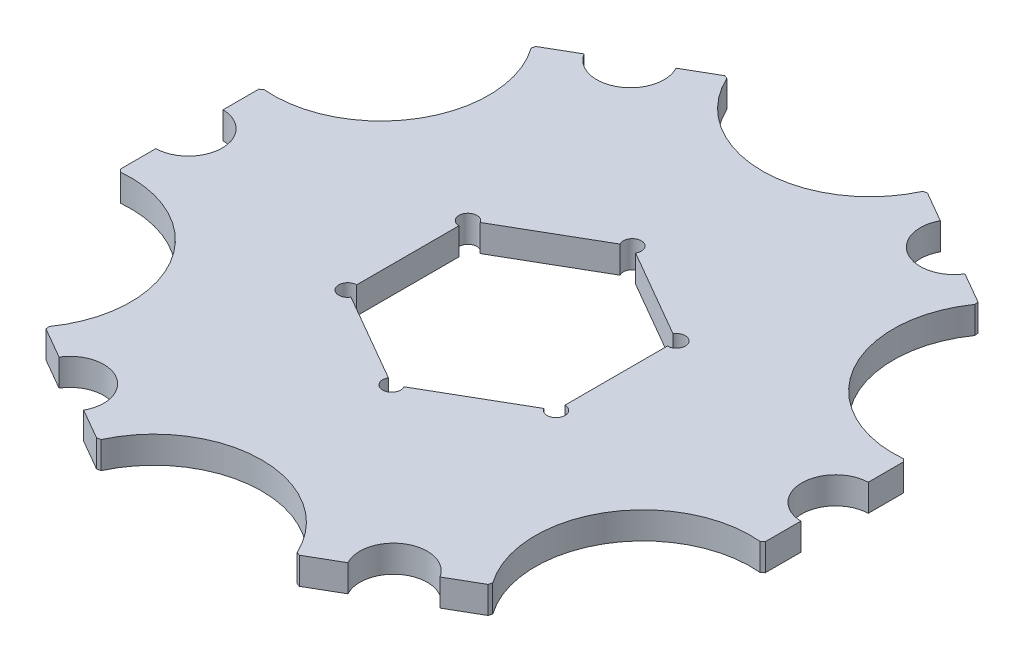
SolidWorks part; units mm, degrees
material "7075-T6 (SN)"
ref_plane "Front Plane" through (0, 0, 0) normal (0, 0, 1) x (1, 0, 0)
ref_plane "Top Plane" through (0, 0, 0) normal (0, 1, 0) x (1, 0, 0)
ref_plane "Right Plane" through (0, 0, 0) normal (1, 0, 0) x (0, 0, -1)
sketch "Sketch1" plane through (0, 0, 0) normal (0, 1, 0) x (1, 0, 0)
  line L0 (0, 0) -> (-62.5623, 0) construction
  line L1 (18.4023, 10.6246) -> (0, 21.2491)
  line L2 (0, 21.2491) -> (-18.4023, 10.6246)
  line L3 (-18.4023, 10.6246) -> (-18.4023, -10.6246)
  line L4 (-18.4023, -10.6246) -> (0, -21.2491)
  line L5 (0, -21.2491) -> (18.4023, -10.6246)
  line L6 (18.4023, -10.6246) -> (18.4023, 10.6246)
  line L7 (-56.9722, 12.7) -> (-56.9722, 5.9505)
  line L8 (-57.15, 0) -> (-57.15, -29.149) construction
  line L9 (-56.9722, -5.9505) -> (-56.9722, -12.7)
  line L10 (-33.6394, 46.3641) -> (-39.4846, 42.9894)
  line L11 (-17.4876, 55.6894) -> (-23.3328, 52.3146)
  line L12 (23.3328, 52.3146) -> (17.4876, 55.6894)
  line L13 (39.4846, 42.9894) -> (33.6394, 46.3641)
  line L14 (56.9722, 5.9505) -> (56.9722, 12.7)
  line L15 (56.9722, -12.7) -> (56.9722, -5.9505)
  line L16 (33.6394, -46.3641) -> (39.4846, -42.9894)
  line L17 (17.4876, -55.6894) -> (23.3328, -52.3146)
  line L18 (-23.3328, -52.3146) -> (-17.4876, -55.6894)
  line L19 (-39.4846, -42.9894) -> (-33.6394, -46.3641)
  circle A0 centre (0, 0) radius 18.4023 construction
  circle A1 centre (-18.4023, 10.6246) radius 1.5875
  arc A2 (-57.15, 5.9531) -> (-57.15, -5.9531) centre (-57.15, 0) ccw construction
  circle A3 centre (0, 21.2491) radius 1.5875
  circle A4 centre (18.4023, 10.6246) radius 1.5875
  circle A5 centre (18.4023, -10.6246) radius 1.5875
  circle A6 centre (0, -21.2491) radius 1.5875
  circle A7 centre (-18.4023, -10.6246) radius 1.5875
  arc A8 (-56.9722, 5.9505) -> (-56.9722, -5.9505) centre (-57.15, 0) cw
  arc A9 (-56.9722, -5.9505) -> (-56.9722, 5.9505) centre (-57.15, 0) ccw construction
  arc A10 (-23.3328, 52.3146) -> (-33.6394, 46.3641) centre (-28.575, 49.4934) cw
  arc A11 (33.6394, 46.3641) -> (23.3328, 52.3146) centre (28.575, 49.4934) cw
  arc A12 (56.9722, -5.9505) -> (56.9722, 5.9505) centre (57.15, 0) cw
  arc A13 (23.3328, -52.3146) -> (33.6394, -46.3641) centre (28.575, -49.4934) cw
  arc A14 (-33.6394, -46.3641) -> (-23.3328, -52.3146) centre (-28.575, -49.4934) cw
  arc A15 (-56.9722, -12.7) -> (-39.4846, -42.9894) centre (-54.7718, -31.6225) cw
  arc A16 (-39.4846, 42.9894) -> (-56.9722, 12.7) centre (-54.7718, 31.6225) cw
  arc A17 (17.4876, 55.6894) -> (-17.4876, 55.6894) centre (0, 63.245) cw
  arc A18 (56.9722, 12.7) -> (39.4846, 42.9894) centre (54.7718, 31.6225) cw
  arc A19 (39.4846, -42.9894) -> (56.9722, -12.7) centre (54.7718, -31.6225) cw
  arc A20 (-17.4876, -55.6894) -> (17.4876, -55.6894) centre (0, -63.245) cw
  point P14 (-50.7998, 29.3293)
  point P27 (0, 0)
  point P58 (0, 0)
  point P74 (0, 0)
  dimension "D1" = 11.9062
  dimension "D4" = 3.175
  dimension "D10" = 19.05
  dimension "D2" = 57.15
  dimension "D3" = 36.8046
  dimension "D6" = 0.3556
  dimension "D7" = 25.4
  dimension "D5" = 6
  dimension "D8" = 6
  dimension "D9" = 6
extrude "Boss-Extrude1" add sketch "Sketch1" along normal blind 4.7625 contours L18 A20 L17 A13 L16 A19 L15 A12 L14 A18 L13 A11 L12 A17 L11 A10 L10 A16 L7 A8 L9 A15 L19 A14 A7 L3 A1 L2 A3 L1 A4 L6 A5 L5 A6 L4 region at (-36.8941, 0, -21.3008)
chamfer "Chamfer1" distance 0.508 angle 45 12 edges at (-56.9722, 2.3813, -12.7) (-56.9722, 2.3813, 12.7) (-39.4846, 2.3813, 42.9894) (-17.4876, 2.3813, 55.6894) (17.4876, 2.3813, 55.6894) (39.4846, 2.3813, 42.9894) (56.9722, 2.3813, 12.7) (56.9722, 2.3813, -12.7) (39.4846, 2.3813, -42.9894) (17.4876, 2.3813, -55.6894) (-17.4876, 2.3813, -55.6894) (-39.4846, 2.3813, -42.9894) first distance on face at (-43.2512, 2.3813, -24.9711) first distance on face at (-56.9722, 2.3813, 9.3252) first distance on face at (-43.2512, 2.3813, 24.9711) first distance on face at (-20.4102, 2.3813, 54.002) first distance on face at (0, 2.3813, 49.9422) first distance on face at (36.562, 2.3813, 44.6768) first distance on face at (43.2512, 2.3813, 24.9711) first distance on face at (56.9722, 2.3813, -9.3252) first distance on face at (43.2512, 2.3813, -24.9711) first distance on face at (20.4102, 2.3813, -54.002) first distance on face at (0, 2.3813, -49.9422) first distance on face at (-36.562, 2.3813, -44.6768)
